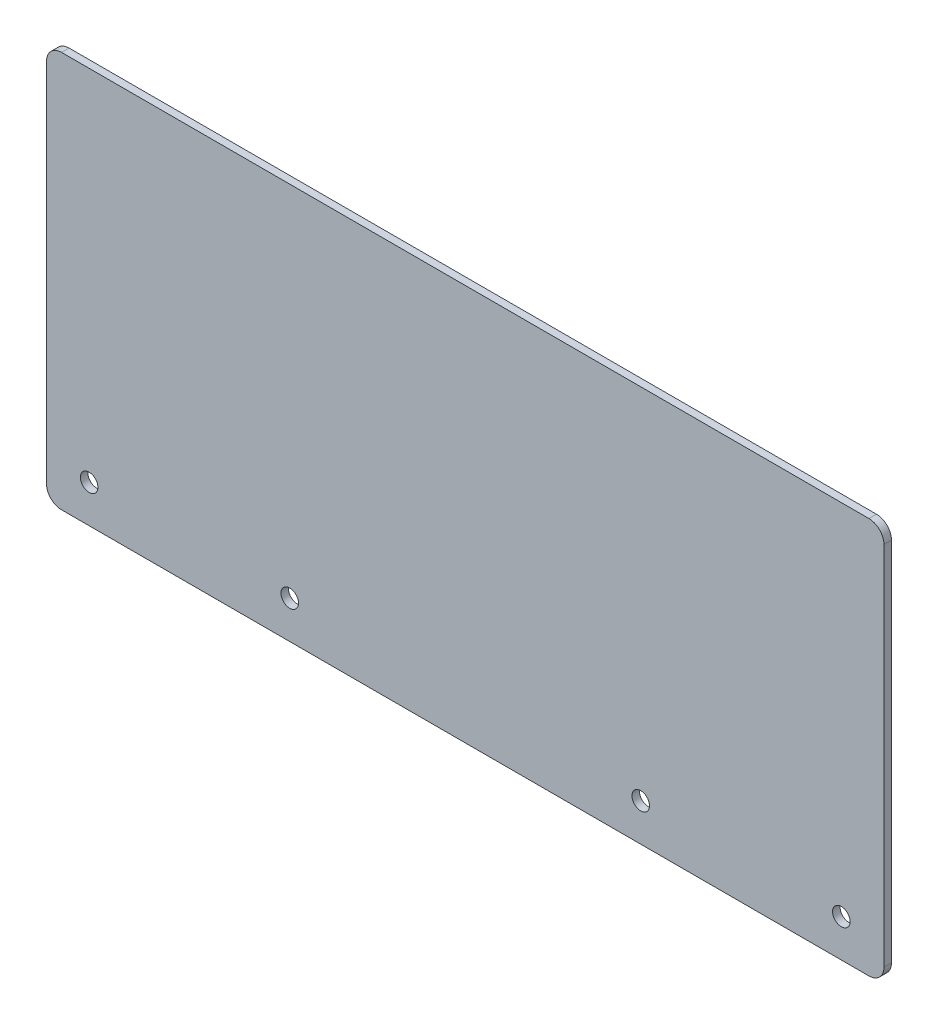
SolidWorks part; units mm, degrees
material "1023 Tôle d'acier au carbone (SS)"
ref_plane "Front" through (0, 0, 0) normal (0, 0, 1) x (1, 0, 0)
ref_plane "Top" through (0, 0, 0) normal (0, 1, 0) x (1, 0, 0)
ref_plane "Right" through (0, 0, 0) normal (1, 0, 0) x (0, 0, -1)
sketch "Esquisse1" plane through (0, 0, 0) normal (0, 0, 1) x (1, 0, 0)
  line L1 (0, 0) -> (167, 0)
  line L2 (0, 0) -> (0, 79)
  line L3 (0, 79) -> (167, 79)
  line L4 (167, 0) -> (167, 79)
  dimension "D1" = 167
  dimension "D2" = 79
extrude "Boss.-Extru.1" add sketch "Esquisse1" along normal blind 1.5
fillet "Congé1" radius 3 4 edges at (167, 0, 0.75) (167, 79, 0.75) (0, 79, 0.75) (0, 0, 0.75)
sketch "Esquisse2" plane through (0, 0, 1.5) normal (0, 0, 1) x (1, 0, 0)
  line L0 (83.5, 79) -> (83.5, 0) construction
  line L1 (164, 79) -> (3, 79) construction
  line L2 (3, 0) -> (164, 0) construction
  line L3 (8.5, 7.5) -> (48.5, 7.5) construction
  line L4 (158.5, 7.5) -> (118.5, 7.5) construction
  circle A0 centre (8.5, 7.5) radius 1.75
  circle A1 centre (48.5, 7.5) radius 1.75
  circle A2 centre (118.5, 7.5) radius 1.75
  circle A3 centre (158.5, 7.5) radius 1.75
  dimension "D1" = 150
  dimension "D2" = 3.5
  dimension "D3" = 7.5
  dimension "D4" = 40
extrude "Enlèv. mat.-Extru.1" cut sketch "Esquisse2" against normal through all both and the other way through all
